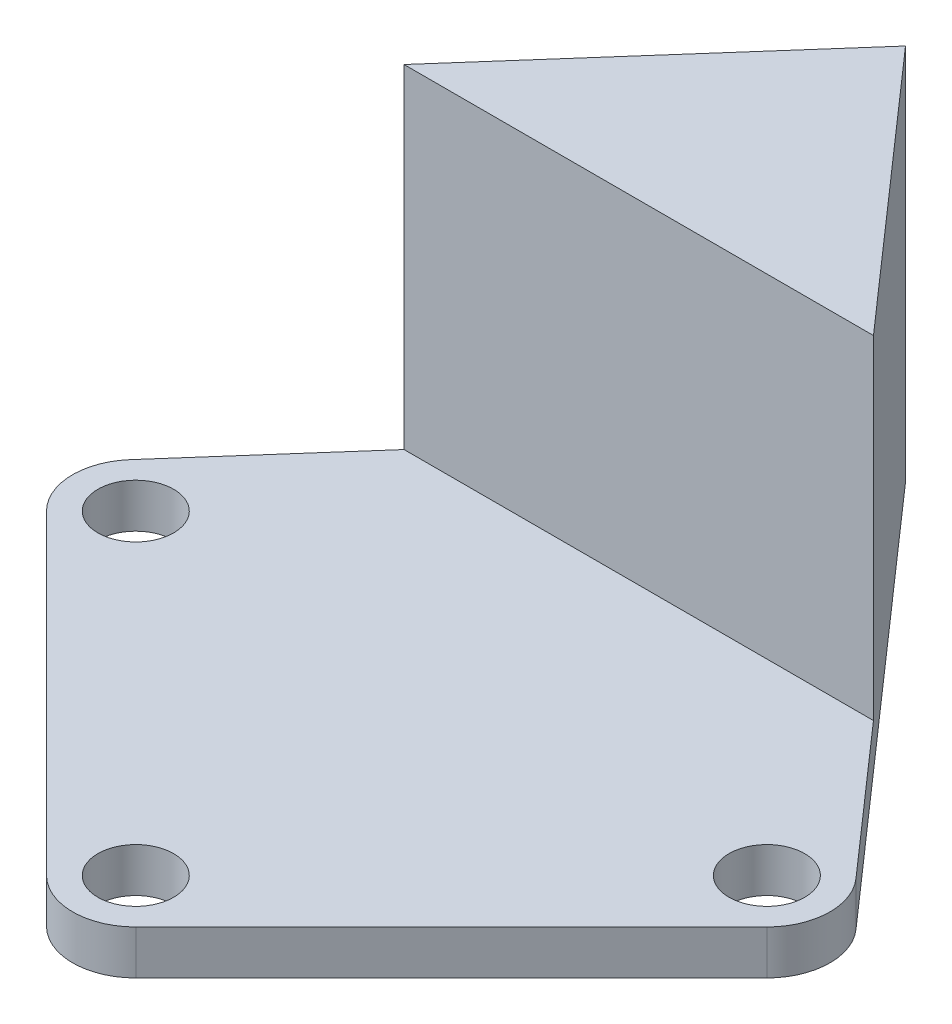
SolidWorks part; units mm, degrees
ref_plane "Front Plane" through (0, 0, 0) normal (0, 0, 1) x (1, 0, 0)
ref_plane "Top Plane" through (0, 0, 0) normal (0, 1, 0) x (1, 0, 0)
ref_plane "Right Plane" through (0, 0, 0) normal (1, 0, 0) x (0, 0, -1)
sketch "Sketch1" plane through (0, 0, 0) normal (0, 1, 0) x (1, 0, 0)
  line L12 (-28.7538, 3.3029) -> (0, 35.9818)
  line L13 (0, 35.9818) -> (28.7538, 3.3029)
  line L14 (28.5355, -3.5355) -> (3.5355, -28.5355)
  line L15 (-3.5355, -28.5355) -> (-28.5355, -3.5355)
  line L16 (-18.5943, 14.8492) -> (18.5943, 14.8492)
  circle A0 centre (0, -25) radius 3
  circle A1 centre (25, 0) radius 3
  circle A2 centre (-25, 0) radius 3
  circle A3 centre (25, 0) radius 5
  circle A4 centre (-25, 0) radius 5
  circle A5 centre (0, -25) radius 5
  dimension "D3" = 6
extrude "Boss-Extrude1" add sketch "Sketch1" along normal blind 3.5 contours A5 L14 A3 L13 L16 L12 A4 L15 | A5 A0 | A4 A2 | A3 A1 | L12 L16 L13 region at (0, 0, 2.497) region at (-23.2848, 0, -4.5458) region at (0, 0, -21.8934) region at (-1.8593, 0, 20.5113) region at (29.5458, 0, -1.7152)
extrude "Boss-Extrude2" add sketch "Sketch1<3>" along normal blind 29.9181 contours L12 L16 L13 region at (0, 0, -21.8934)
sketch "Sketch1<3>" plane through (0, 0, 0) normal (0, 1, 0) x (1, 0, 0) same geometry as "Sketch1"
sketch "Sketch3" plane through (0, 29.9181, 0) normal (0, 1, 0) x (1, 0, 0)
  line L0 (0, 31.4403) -> (-11.9587, 17.8492)
  line L1 (-11.9587, 17.8492) -> (11.9587, 17.8492)
  line L2 (11.9587, 17.8492) -> (0, 31.4403)
  line L3 (0, 35.9818) -> (-18.5943, 14.8492)
  line L4 (-18.5943, 14.8492) -> (18.5943, 14.8492)
  line L5 (18.5943, 14.8492) -> (0, 35.9818)
  line L6 (0, 35.9818) -> (-18.5943, 14.8492)
  line L7 (-18.5943, 14.8492) -> (18.5943, 14.8492)
  line L8 (18.5943, 14.8492) -> (0, 35.9818)
  dimension "D1" = 0
  dimension "D2" = 3
extrude "Cut-Extrude1" cut sketch "Sketch3" against normal blind 28.5 from offset 3.5 contours L1 L2 L0 region at (0, 29.9181, -22.3796) offset against normal yes
